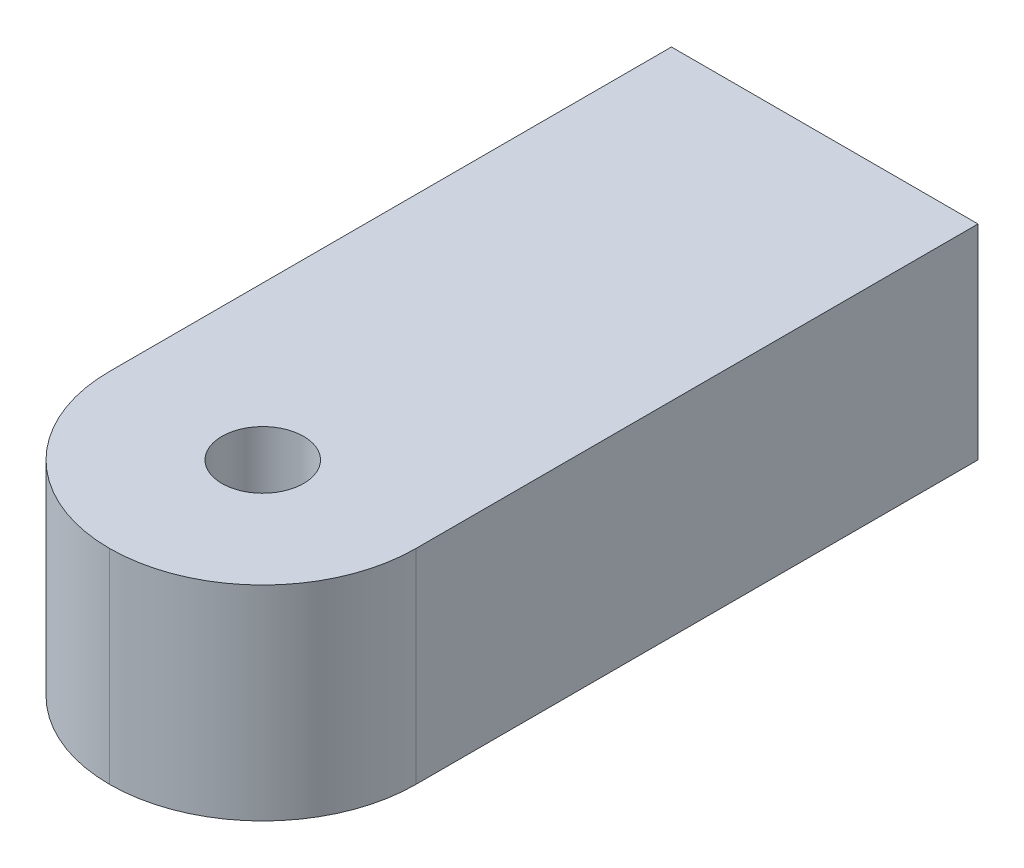
SolidWorks part; units mm, degrees
ref_plane "Front Plane" through (0, 0, 0) normal (0, 0, 1) x (1, 0, 0)
ref_plane "Top Plane" through (0, 0, 0) normal (0, 1, 0) x (1, 0, 0)
ref_plane "Right Plane" through (0, 0, 0) normal (1, 0, 0) x (0, 0, -1)
sketch "Sketch1" plane through (0, 0, 0) normal (0, 0, 1) x (1, 0, 0)
  line L1 (7.5, 5) -> (-7.5, 5)
  line L2 (7.5, 5) -> (7.5, -5)
  line L3 (7.5, -5) -> (-7.5, -5)
  line L4 (-7.5, 5) -> (-7.5, -5)
  line L5 (7.5, 5) -> (-7.5, -5) construction
  line L6 (7.5, -5) -> (-7.5, 5) construction
  point P0 (0, 0)
  dimension "D1" = 15
  dimension "D2" = 10
extrude "Boss-Extrude1" add sketch "Sketch1" along normal blind 35 contours L1 L4 L3 L2
fillet "Fillet1" radius 7.5 2 edges at (7.5, 0, 35) (-7.5, 0, 35)
sketch "Sketch2" plane through (0, 5, 0) normal (0, 1, 0) x (1, 0, 0)
  circle A0 centre (0, -27.5) radius 2
  dimension "D1" = 4
extrude "Cut-Extrude1" cut sketch "Sketch2" against normal through all both and the other way through all
